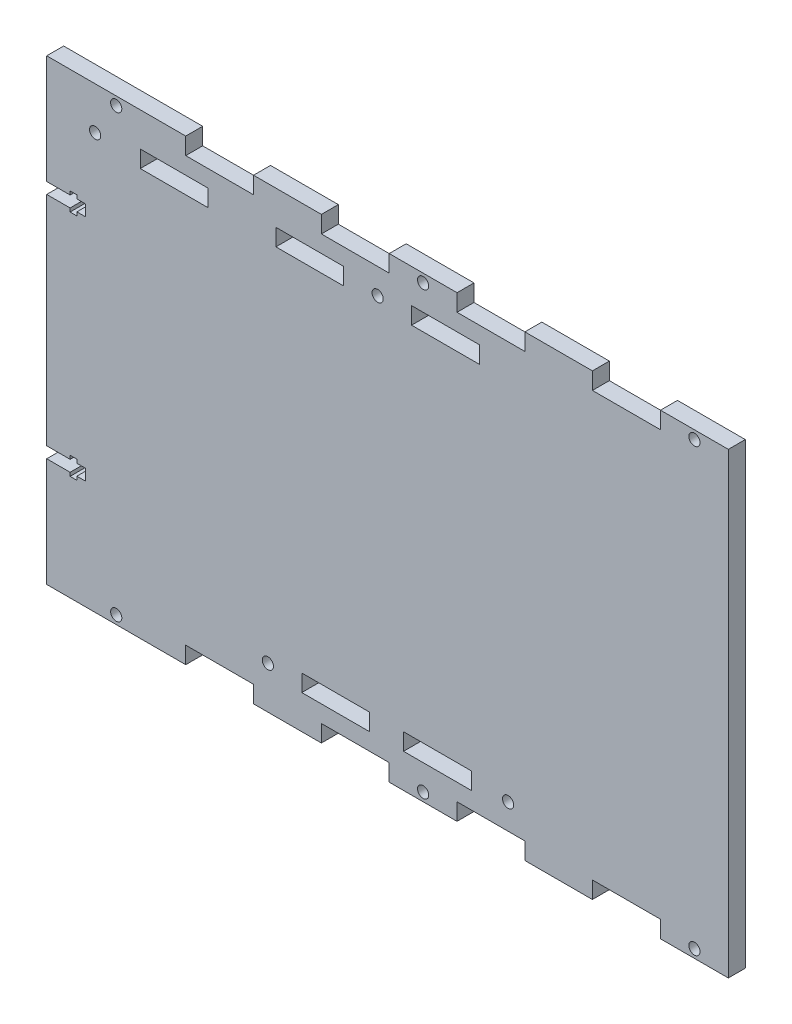
SolidWorks part; units mm, degrees
ref_plane "Front Plane" through (0, 0, 0) normal (0, 0, 1) x (1, 0, 0)
ref_plane "Top Plane" through (0, 0, 0) normal (0, 1, 0) x (1, 0, 0)
ref_plane "Right Plane" through (0, 0, 0) normal (1, 0, 0) x (0, 0, -1)
sketch "Sketch1" plane through (0, 0, 0) normal (0, 0, 1) x (1, 0, 0)
  line L1 (115.91, -15.875) -> (-139.3499, -15.875)
  line L2 (115.91, -15.875) -> (115.91, 155.575)
  line L3 (115.91, 155.575) -> (-139.3499, 155.575)
  line L4 (-139.3499, -15.875) -> (-139.3499, 155.575)
  line L5 (113.7824, 69.85) -> (-193.0608, 69.85) construction
extrude "Boss-Extrude1" add sketch "Sketch1" along normal blind 6.35
sketch "Sketch8" plane through (0, 0, 0) normal (0, 0, -1) x (-1, 0, 0)
  line L0 (139.3499, -15.875) -> (-115.91, -15.875) construction
  line L1 (-90.51, -9.525) -> (-65.0002, -9.525)
  line L2 (-90.51, -9.525) -> (-90.51, -15.875)
  line L3 (-90.51, -15.875) -> (-65.0002, -15.875)
  line L4 (-65.0002, -9.525) -> (-65.0002, -15.875)
  line L5 (-14.31, -15.875) -> (-14.31, -9.525) construction
  line L6 (-39.71, -9.525) -> (-14.31, -9.525)
  line L7 (-39.71, -9.525) -> (-39.71, -15.875)
  line L8 (-39.71, -15.875) -> (-14.31, -15.875)
  line L9 (-14.31, -9.525) -> (-14.31, -15.875)
  line L10 (87.29, -15.875) -> (87.29, -9.525) construction
  line L11 (11.09, -9.525) -> (36.49, -9.525)
  line L12 (11.09, -9.525) -> (11.09, -15.875)
  line L13 (11.09, -15.875) -> (36.49, -15.875)
  line L14 (36.49, -9.525) -> (36.49, -15.875)
  line L15 (61.89, -9.525) -> (87.29, -9.525)
  line L16 (61.89, -9.525) -> (61.89, -15.875)
  line L17 (61.89, -15.875) -> (87.29, -15.875)
  line L18 (87.29, -9.525) -> (87.29, -15.875)
  line L19 (-115.91, 155.575) -> (139.3499, 155.575) construction
  line L20 (-90.51, 149.225) -> (-65.0002, 149.225)
  line L21 (-90.51, 149.225) -> (-90.51, 155.575)
  line L22 (-90.51, 155.575) -> (-65.0002, 155.575)
  line L23 (-65.0002, 149.225) -> (-65.0002, 155.575)
  line L25 (-39.71, 149.225) -> (-14.31, 149.225)
  line L26 (-39.71, 149.225) -> (-39.71, 155.575)
  line L27 (-39.71, 155.575) -> (-14.31, 155.575)
  line L28 (-14.31, 149.225) -> (-14.31, 155.575)
  line L29 (11.09, 149.225) -> (36.49, 149.225)
  line L30 (11.09, 149.225) -> (11.09, 155.575)
  line L31 (11.09, 155.575) -> (36.49, 155.575)
  line L32 (36.49, 149.225) -> (36.49, 155.575)
  line L33 (61.89, 149.225) -> (87.29, 149.225)
  line L34 (61.89, 149.225) -> (61.89, 155.575)
  line L35 (61.89, 155.575) -> (87.29, 155.575)
  line L36 (87.29, 149.225) -> (87.29, 155.575)
extrude "Cut-Extrude5" cut sketch "Sketch8" against normal through all
sketch "Sketch11" plane through (0, 0, 6.35) normal (0, 0, 1) x (1, 0, 0)
  line L0 (-139.3499, 69.85) -> (115.91, 69.85) construction
  line L1 (-139.3499, 155.575) -> (-139.3499, -15.875) construction
  line L2 (115.91, -15.875) -> (115.91, 155.575) construction
  line L3 (-115.4535, -9.525) -> (-111.1863, -15.875) construction
  line L4 (-139.3499, -15.875) -> (-87.29, -15.875) construction
  line L5 (-111.1863, -9.525) -> (-111.1863, -15.875) construction
  line L6 (-111.1863, -9.525) -> (-115.4535, -15.875) construction
  line L7 (-115.4535, -9.525) -> (-115.4535, -15.875) construction
  line L8 (3.7436, -9.525) -> (-0.5236, -15.875) construction
  line L9 (-11.09, -15.875) -> (14.31, -15.875) construction
  line L10 (-0.5236, -9.525) -> (-0.5236, -15.875) construction
  line L11 (-0.5236, -9.525) -> (3.7436, -15.875) construction
  line L12 (3.7436, -9.525) -> (3.7436, -15.875) construction
  line L13 (101.0764, -9.525) -> (105.3436, -15.875) construction
  line L14 (90.51, -15.875) -> (115.91, -15.875) construction
  line L15 (105.3436, -9.525) -> (105.3436, -15.875) construction
  line L16 (105.3436, -9.525) -> (101.0764, -15.875) construction
  circle A0 centre (103.21, -12.7) radius 2.0955
  circle A1 centre (1.61, -12.7) radius 2.0955
  circle A2 centre (-113.3199, -12.7) radius 2.0955
  circle A3 centre (103.21, 152.4) radius 2.0955
  circle A4 centre (1.61, 152.4) radius 2.0955
  circle A5 centre (-113.3199, 152.4) radius 2.0955
  dimension "D3" = 4.191
extrude "Cut-Extrude7" cut sketch "Sketch11" against normal through all
sketch "Sketch12" plane through (0, 0, 6.35) normal (0, 0, 1) x (1, 0, 0)
  line L1 (-43.831, -3.175) -> (-18.431, -3.175)
  line L2 (-43.831, -3.175) -> (-43.831, 3.175)
  line L3 (-43.831, 3.175) -> (-18.431, 3.175)
  line L4 (-18.431, -3.175) -> (-18.431, 3.175)
  line L5 (-5.731, -3.175) -> (19.669, -3.175)
  line L6 (-5.731, -3.175) -> (-5.731, 3.175)
  line L7 (-5.731, 3.175) -> (19.669, 3.175)
  line L8 (19.669, -3.175) -> (19.669, 3.175)
extrude "Cut-Extrude8" cut sketch "Sketch12" against normal through all
sketch "Sketch13" plane through (0, 0, 6.35) normal (0, 0, 1) x (1, 0, 0)
  line L1 (-104.3134, 136.525) -> (-78.9174, 136.525)
  line L2 (-104.3134, 136.525) -> (-104.3134, 142.875)
  line L3 (-104.3134, 142.875) -> (-78.9174, 142.875)
  line L4 (-78.9174, 136.525) -> (-78.9174, 142.875)
  line L5 (-53.5134, 136.525) -> (-28.1134, 136.525)
  line L6 (-53.5134, 136.525) -> (-53.5134, 142.875)
  line L7 (-53.5134, 142.875) -> (-28.1134, 142.875)
  line L8 (-28.1134, 136.525) -> (-28.1134, 142.875)
  line L9 (-2.7134, 136.525) -> (22.6866, 136.525)
  line L10 (-2.7134, 136.525) -> (-2.7134, 142.875)
  line L11 (-2.7134, 142.875) -> (22.6866, 142.875)
  line L12 (22.6866, 136.525) -> (22.6866, 142.875)
extrude "Cut-Extrude9" cut sketch "Sketch13" against normal through all
sketch "Sketch14" plane through (0, 0, 0) normal (0, 0, -1) x (-1, 0, 0)
  line L0 (-35.5594, 3.175) -> (-31.2922, -3.175) construction
  line L1 (-31.2922, 3.175) -> (-35.5594, -3.175) construction
  line L2 (54.3974, 3.175) -> (58.6646, -3.175) construction
  line L3 (54.3974, -3.175) -> (58.6646, 3.175) construction
  line L4 (119.0785, 142.875) -> (123.3457, 136.525) construction
  line L5 (119.0785, 136.525) -> (123.3457, 142.875) construction
  line L6 (13.2798, 142.875) -> (17.547, 136.525) construction
  line L7 (13.2798, 136.525) -> (17.547, 142.875) construction
  line L8 (139.3499, 69.85) -> (108.0426, 69.85) construction
  line L9 (-115.91, -15.875) -> (-115.91, 155.575) construction
  line L10 (-115.91, -15.875) -> (-115.91, 69.85) construction
  line L11 (139.3499, 155.575) -> (139.3499, -15.875) construction
  line L12 (-115.91, 69.85) -> (-115.91, 155.575) construction
  line L13 (139.3499, 69.85) -> (139.3499, 155.575) construction
  line L14 (139.3499, 112.7125) -> (121.2121, 112.7125) construction
  line L15 (139.3499, 69.85) -> (139.3499, -15.875) construction
  line L16 (139.3499, 26.9875) -> (117.955, 26.9875) construction
  circle A0 centre (-33.4258, 0) radius 2.0955
  circle A1 centre (56.531, 0) radius 2.0955
  circle A2 centre (121.2121, 139.7) radius 2.0955
  circle A3 centre (15.4134, 139.7) radius 2.0955
  line B0 (139.3499, 24.892) -> (139.3499, 29.083)
  line B1 (128.0469, 29.083) -> (128.0469, 30.4165)
  line B2 (128.0469, 30.4165) -> (130.5869, 30.4165)
  line B3 (130.5869, 30.4165) -> (130.5869, 29.083)
  line B4 (130.5869, 29.083) -> (139.3499, 29.083)
  line B5 (128.0469, 29.083) -> (124.7449, 29.083)
  line B6 (124.7449, 29.083) -> (124.7449, 24.892)
  line B7 (128.0469, 24.892) -> (124.7449, 24.892)
  line B8 (130.5869, 24.892) -> (139.3499, 24.892)
  line B9 (130.5869, 23.5585) -> (130.5869, 24.892)
  line B10 (128.0469, 23.5585) -> (130.5869, 23.5585)
  line B11 (128.0469, 24.892) -> (128.0469, 23.5585)
  line B12 (139.3499, 110.617) -> (139.3499, 114.808)
  line B13 (128.0469, 114.808) -> (128.0469, 116.1415)
  line B14 (128.0469, 116.1415) -> (130.5869, 116.1415)
  line B15 (130.5869, 116.1415) -> (130.5869, 114.808)
  line B16 (130.5869, 114.808) -> (139.3499, 114.808)
  line B17 (128.0469, 114.808) -> (124.7449, 114.808)
  line B18 (124.7449, 114.808) -> (124.7449, 110.617)
  line B19 (128.0469, 110.617) -> (124.7449, 110.617)
  line B20 (130.5869, 110.617) -> (139.3499, 110.617)
  line B21 (130.5869, 109.2835) -> (130.5869, 110.617)
  line B22 (128.0469, 109.2835) -> (130.5869, 109.2835)
  line B23 (128.0469, 110.617) -> (128.0469, 109.2835)
  dimension "D1" = 4.191
sketch_block_instance "TSlot-4"
sketch_block "TSlot" parameters "D1"=3.302, "D2"=2.54, "D3"=3.175, "D4"=8.763, "D5"=1.3462
sketch_block_instance "TSlot-6"
extrude "Cut-Extrude10" cut sketch "Sketch14" against normal through all
